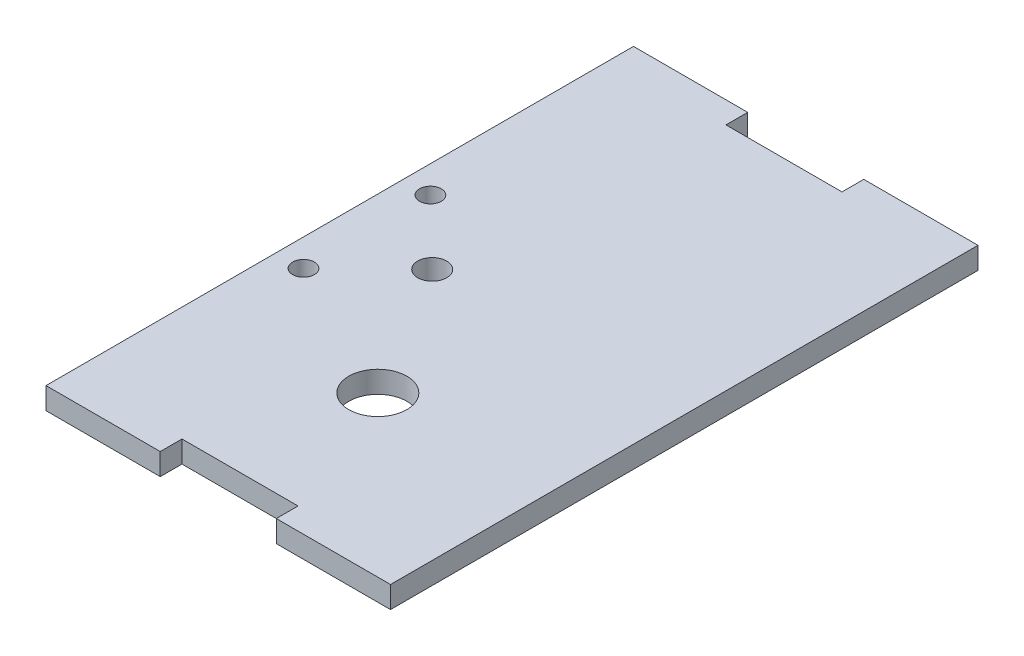
SolidWorks part; units mm, degrees
ref_plane "Alzado" through (0, 0, 0) normal (0, 0, 1) x (1, 0, 0)
ref_plane "Planta" through (0, 0, 0) normal (0, 1, 0) x (1, 0, 0)
ref_plane "Vista lateral" through (0, 0, 0) normal (1, 0, 0) x (0, 0, -1)
sketch "Croquis1" plane through (0, 0, 0) normal (0, 1, 0) x (1, 0, 0)
  line L0 (0, 0) -> (15.75, 0)
  line L1 (47.5, 0) -> (47.5, 81)
  line L2 (23.75, 3) -> (15.75, 3)
  line L3 (15.75, 3) -> (15.75, 0)
  line L4 (23.75, 3) -> (31.75, 3)
  line L5 (31.75, 3) -> (31.75, 0)
  line L6 (47.5, 40.5) -> (38.6194, 40.5) construction
  line L7 (31.75, 78) -> (31.75, 81)
  line L8 (23.75, 78) -> (31.75, 78)
  line L9 (15.75, 78) -> (15.75, 81)
  line L10 (23.75, 78) -> (15.75, 78)
  line L11 (47.5, 81) -> (31.75, 81)
  line L12 (0, 81) -> (0, 0)
  line L13 (23.75, 78) -> (23.75, 3) construction
  line L14 (38.6194, 40.5) -> (23.75, 40.5) construction
  line L15 (23.75, 40.5) -> (3.75, 40.5) construction
  line L16 (3.75, 40.5) -> (3.75, 49.25) construction
  line L17 (23.75, 40.5) -> (12.75, 40.5) construction
  line L18 (15.75, 81) -> (0, 81)
  line L19 (31.75, 0) -> (47.5, 0)
  line L20 (23.75, 40.5) -> (23.75, 22) construction
  circle A0 centre (3.75, 49.25) radius 1.5
  circle A1 centre (3.75, 31.75) radius 1.5
  circle A2 centre (12.75, 40.5) radius 2
  circle A3 centre (23.75, 22) radius 4
  dimension "D7" = 3
  dimension "D9" = 4
  dimension "D11" = 8
  dimension "D1" = 47.5
  dimension "D2" = 81
  dimension "D3" = 8
  dimension "D4" = 8
  dimension "D5" = 20
  dimension "D6" = 8.75
  dimension "D8" = 11
  dimension "D10" = 18.5
extrude "Saliente-Extruir1" add sketch "Croquis1" along normal blind 3
